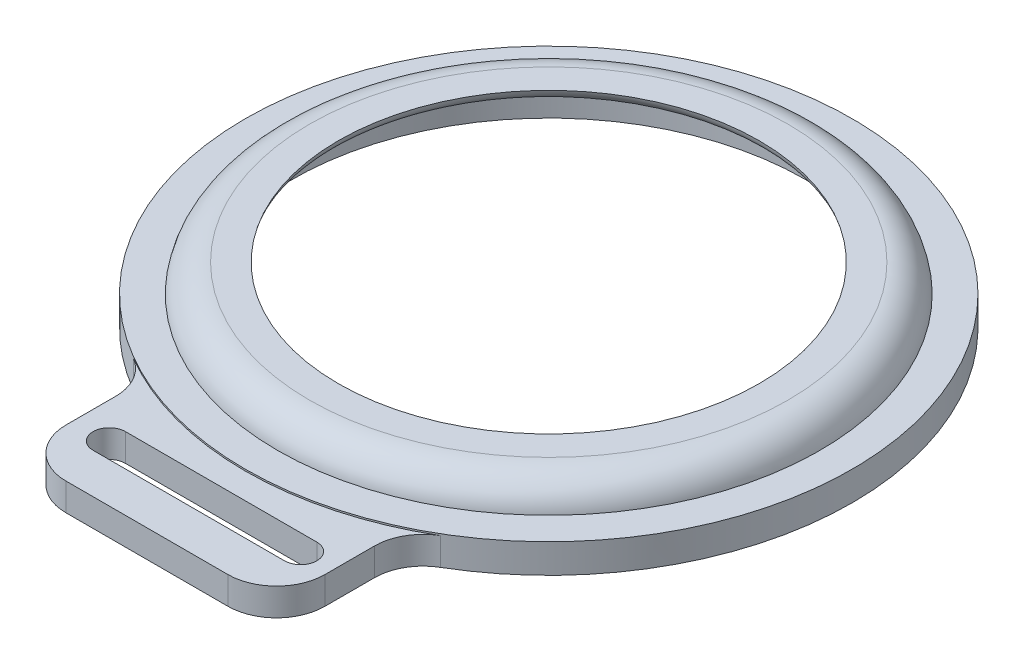
SolidWorks part; units mm, degrees
ref_plane "Front Plane" through (0, 0, 0) normal (0, 0, 1) x (1, 0, 0)
ref_plane "Top Plane" through (0, 0, 0) normal (0, 1, 0) x (1, 0, 0)
ref_plane "Right Plane" through (0, 0, 0) normal (1, 0, 0) x (0, 0, -1)
sketch "Sketch1" plane through (0, 0, 0) normal (0, 1, 0) x (1, 0, 0)
  circle A0 centre (0, 0) radius 18.75
  dimension "D1" = 37.5
extrude "Boss-Extrude1" add sketch "Sketch1" along normal blind 1.8
sketch "Sketch2" plane through (0, 1.8, 0) normal (0, 1, 0) x (1, 0, 0)
  circle A0 centre (0, 0) radius 16.75
  dimension "D1" = 33.5
extrude "Boss-Extrude2" add sketch "Sketch2" along normal blind 1.7
sketch "Sketch3" plane through (0, 3.5, 0) normal (0, 1, 0) x (1, 0, 0)
  circle A0 centre (0, 0) radius 13
  dimension "D1" = 26
extrude "Cut-Extrude1" cut sketch "Sketch3" against normal blind 5.7
fillet "Fillet1" radius 2 1 edges at (0, 3.5, 16.75)
sketch "Sketch4" plane through (0, 0, 0) normal (0, -1, 0) x (1, 0, 0)
  circle A0 centre (0, 0) radius 15.85
  dimension "D1" = 31.7
extrude "Cut-Extrude2" cut sketch "Sketch4" against normal blind 2.7
fillet "Fillet2" radius 1 2 edges at (0, 2.7, -13) (0, 2.7, -15.85)
sketch "Sketch5" plane through (0, 0, 0) normal (0, -1, 0) x (1, 0, 0)
  line L0 (-8, 18.7633) -> (-8, 21.8206)
  line L3 (-5, 24.8206) -> (5, 24.8206)
  line L5 (-5.8085, 21.3381) -> (6.0159, 21.3381) construction
  line L6 (-5.8085, 22.3381) -> (6.0159, 22.3381)
  line L7 (-5.8085, 20.3381) -> (6.0159, 20.3381)
  line L9 (8, 18.7633) -> (8, 21.8206)
  arc A0 (-5.8085, 22.3381) -> (-5.8085, 20.3381) centre (-5.8085, 21.3381) ccw
  arc A1 (-9.4828, 16.1753) -> (9.4828, 16.1753) centre (0, 0) cw
  arc A3 (6.0159, 20.3381) -> (6.0159, 22.3381) centre (6.0159, 21.3381) ccw
  arc A4 (-8, 18.7633) -> (-9.4828, 16.1753) centre (-11, 18.7633) cw
  arc A5 (8, 18.7633) -> (9.4828, 16.1753) centre (11, 18.7633) ccw
  arc A6 (5, 24.8206) -> (8, 21.8206) centre (5, 21.8206) cw
  arc A7 (-8, 21.8206) -> (-5, 24.8206) centre (-5, 21.8206) cw
  point P0 (0, 0)
  point P6 (0.1037, 21.3381)
  point P25 (8, 24.8206)
  point P28 (-8, 24.8206)
  dimension "D4" = 3
  dimension "D5" = 3
  dimension "D1" = 16
  dimension "D3" = 2
extrude "Boss-Extrude3" add sketch "Sketch5" against normal blind 1.7
